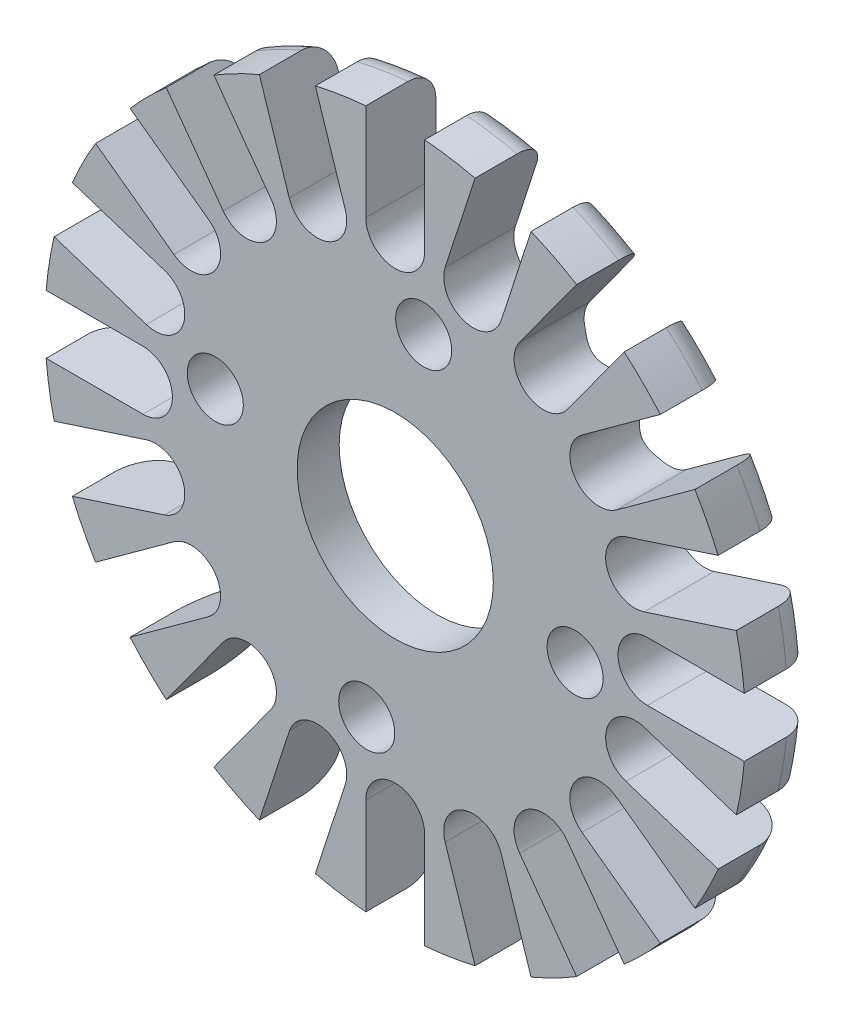
SolidWorks part; units mm, degrees
material "7075-T6，板材(SS)"
ref_plane "前视基准面" through (0, 0, 0) normal (0, 0, 1) x (1, 0, 0)
ref_plane "上视基准面" through (0, 0, 0) normal (0, 1, 0) x (1, 0, 0)
ref_plane "右视基准面" through (0, 0, 0) normal (1, 0, 0) x (0, 0, -1)
sketch "草图1" plane through (0, 0, 0) normal (0, 0, 1) x (1, 0, 0)
  circle A0 centre (0, 0) radius 25
  dimension "D1" = 50
extrude "拉伸1" add sketch "草图1" along normal blind 5
sketch "草图2" plane through (0, 0, 5) normal (0, 0, 1) x (1, 0, 0)
  circle A0 centre (0, 0) radius 7
  dimension "D1" = 14
extrude "拉伸2" cut sketch "草图2" against normal blind 3
sketch "草图3" plane through (0, 0, 5) normal (0, 0, 1) x (1, 0, 0)
  line L0 (2.0336, 12.8399) -> (0, 0) construction
  line L1 (0, 0) -> (0, 13) construction
  circle A0 centre (2.0336, 12.8399) radius 2
  circle A1 centre (0, 0) radius 13 construction
  dimension "D1" = 26
  dimension "D2" = 4
  dimension "D3" = 9
extrude "拉伸3" cut sketch "草图3" against normal blind 3
pattern_circular "阵列(圆周)1" count 4 every 90 about axis through (0, 0, 2) along (0, 0, 1) of "拉伸3"
sketch "草图4" plane through (0, 0, 5) normal (0, 0, 1) x (1, 0, 0)
  line L0 (-18, 2.1) -> (-24.9116, 2.1)
  line L1 (-18, -2.1) -> (-24.9116, -2.1)
  circle A0 centre (0, 0) radius 18 construction
  arc A1 (-18, -2.1) -> (-18, 2.1) centre (-18, 0) ccw
  circle A2 centre (0, 0) radius 25 construction
  arc A4 (-24.9116, 2.1) -> (-24.9116, -2.1) centre (0, 0) ccw
  dimension "D1" = 36
  dimension "D2" = 4.2
extrude "拉伸4" cut sketch "草图4" against normal through all
pattern_circular "阵列(圆周)3" count 20 over 360 about axis through (0, 0, 2) along (0, 0, 1) of "拉伸4"
sketch "草图5" plane through (0, 0, 0) normal (0, 0, -1) x (-1, 0, 0)
  circle A0 centre (0, 0) radius 15.5
  dimension "D1" = 31
extrude "切除-拉伸1" cut sketch "草图5" against normal blind 2
fillet "圆角1" radius 1 1 edges at (-15.5, 0, 0)
fillet "圆角2" radius 2 20 edges at (24.6922, 3.9109, 0) (22.2752, 11.3498, 0) (17.6777, 17.6777, 0) (11.3498, 22.2752, 0) (3.9109, 24.6922, 0) (-3.9109, 24.6922, 0) (-24.6922, 3.9109, 0) (-24.6922, -3.9109, 0) (-22.2752, -11.3498, 0) (-17.6777, -17.6777, 0) (-11.3498, -22.2752, 0) (-3.9109, -24.6922, 0) (3.9109, -24.6922, 0) (11.3498, -22.2752, 0) (17.6777, -17.6777, 0) (22.2752, -11.3498, 0) (24.6922, -3.9109, 0) (-22.2752, 11.3498, 0) (-17.6777, 17.6777, 0) (-11.3498, 22.2752, 0)
sketch "草图7" plane through (0, 0, 2) normal (0, 0, -1) x (-1, 0, 0)
  circle A0 centre (0, 0) radius 13
  circle A1 centre (-2.0336, 12.8399) radius 3
extrude "切除-拉伸2" cut sketch "草图7" along normal through all contours A1
pattern_circular "阵列(圆周)4" count 4 over 360 about axis through (0, 0, 2) along (0, 0, -1) of "切除-拉伸2"
